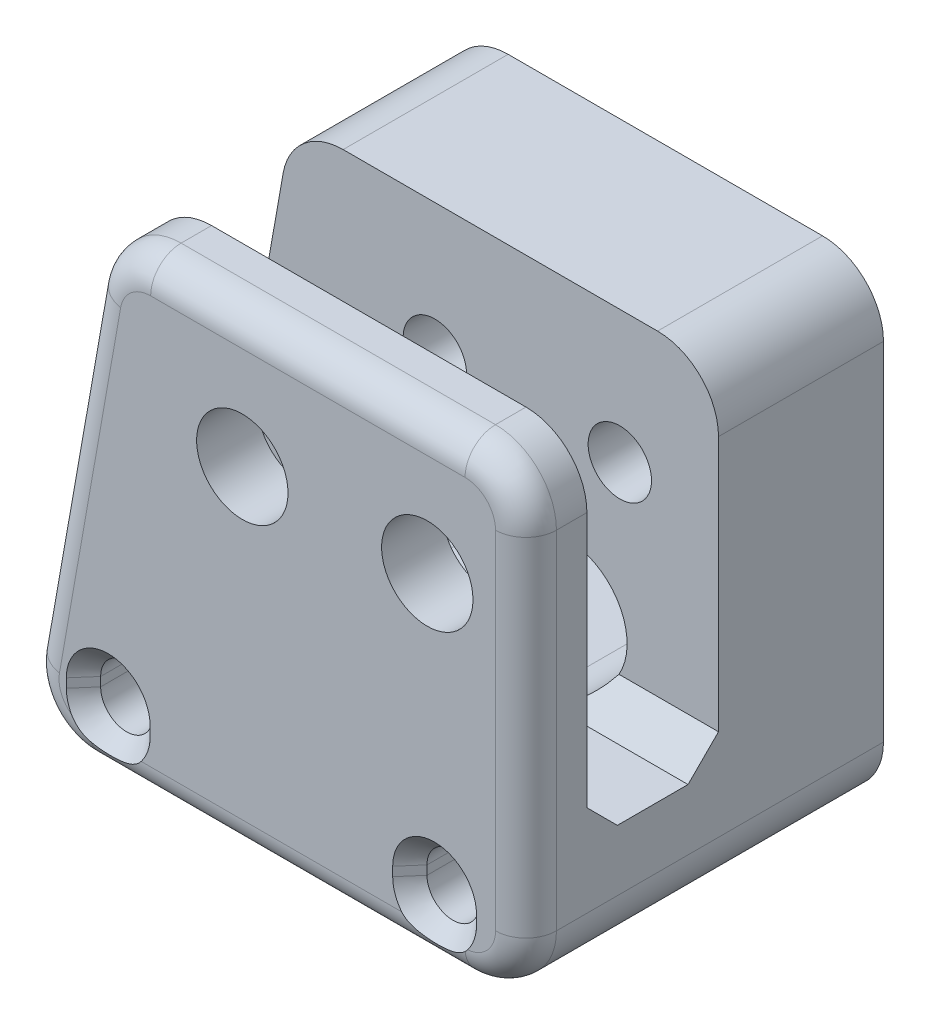
SolidWorks part; units mm, degrees
material "PET"
ref_plane "Front Plane" through (0, 0, 0) normal (0, 0, 1) x (1, 0, 0)
ref_plane "Top Plane" through (0, 0, 0) normal (0, 1, 0) x (1, 0, 0)
ref_plane "Right Plane" through (0, 0, 0) normal (1, 0, 0) x (0, 0, -1)
sketch "Sketch1" plane through (0, 0, 0) normal (0, 0, 1) x (1, 0, 0)
  line L0 (9.9949, 9.271) -> (9.9949, -24.688) construction
  line L2 (9.9949, 9.271) -> (9.9949, -15.163)
  line L3 (9.9949, 9.271) -> (-12.2301, 9.271)
  line L4 (-12.2301, 9.271) -> (-16.5385, -15.163)
  line L5 (-16.5385, -15.163) -> (9.9949, -15.163)
  point P3 (0, 0)
  point P4 (0, 0)
  point P5 (0, 0)
  point P9 (0, 0)
  point P11 (0, 0)
  point P12 (0, 0)
  dimension "D1" = 9.525
  dimension "D2" = 80
  dimension "D3" = 22.225
extrude "Boss-Extrude1" add sketch "Sketch1" along normal blind 3.175
extrude "Boss-Extrude2" add sketch "Sketch1<2>" against normal up to surface (8.5979 mm away) from offset 6.858 separate body offset against normal yes
sketch "Sketch1<2>" plane through (0, 0, 0) normal (0, 0, 1) x (1, 0, 0) same geometry as "Sketch1"
sketch "Sketch3" plane through (0, 0, -6.858) normal (0, 0, 1) x (1, 0, 0)
  line L0 (9.9949, 9.271) -> (9.9949, -15.163) construction
  line L1 (-16.5385, -15.163) -> (-12.2301, 9.271) construction
  line L2 (9.9949, -15.163) -> (-16.5385, -15.163) construction
  line L3 (9.9949, -8.813) -> (9.9949, -15.163)
  line L4 (-16.5385, -15.163) -> (-15.4188, -8.813)
  line L5 (9.9949, -15.163) -> (-16.5385, -15.163)
  line L6 (9.9949, -8.813) -> (-15.4188, -8.813)
  dimension "D1" = 6.35
extrude "Boss-Extrude3" add sketch "Sketch3" along normal up to surface (6.858 mm away) up to face at (-2.1947, -2.946, 0)
hole_wizard "CSK SLOT for #2 Flat Head Machine Screw1" positions "Sketch4" profile "Sketch5" size "#2" standard "ANSI Inch" slot yes end condition through all
sketch "Sketch4" plane through (0, 0, 3.175) normal (0, 0, 1) x (1, 0, 0)
  line L0 (5.2324, -13.5755) -> (5.2324, -10.4005) construction
  line L1 (9.9949, -15.163) -> (9.9949, 9.271) construction
  line L2 (-16.5385, -15.163) -> (9.9949, -15.163) construction
  point P0 (5.2324, -11.988)
  point P2 (-11.776, -11.988)
  dimension "D1" = 3.175
  dimension "D2" = 3.175
  dimension "D3" = 4.7625
  dimension "D4" = 4.7625
sketch "Sketch5" plane through (5.2324, -11.988, 3.175) normal (1, 0, 0) x (0, -1, 0)
  line L0 (0, 0) -> (0, 18.6309)
  line L1 (0, 18.6309) -> (1.3525, 18.6309)
  line L2 (1.3525, 18.6309) -> (1.3525, 0.9569)
  line L3 (1.3525, 0.9569) -> (2.1844, 0)
  line L5 (2.1844, 0) -> (0, 0)
  line L6 (-1.3525, 0.9569) -> (-2.1844, 0) construction
  line L11 (0, -6.35) -> (0, 107.95) construction
  dimension "Thru Hole Dia." = 2.7051
  dimension "Thru Hole Depth" = 18.6309
  dimension "Near C'Sink Dia." = 4.3688
  dimension "Near C'Sink Angle" = 82
fillet "Fillet1" radius 3.175 6 edges at (-12.2301, 9.271, -11.157) (-12.2301, 9.271, 1.5875) (9.9949, 9.271, 1.5875) (9.9949, 9.271, -11.157) (9.9949, -15.163, -6.1405) (-16.5385, -15.163, -6.1405)
chamfer "Chamfer1" distance 1.5875 angle 45 2 edges at (-2.7119, -8.813, 0) (-2.7119, -8.813, -6.858)
hole_wizard "3/16 (0.1875) Diameter Hole1" positions "Sketch6" profile "Sketch7" hole size "3/16" standard "ANSI Inch" end condition up to next
sketch "Sketch6" plane through (0, 0, 3.175) normal (0, 0, 1) x (1, 0, 0)
  point P0 (4.8514, 2.3622)
  point P3 (-4.7879, 2.3622)
sketch "Sketch7" plane through (4.8514, 2.3622, 3.175) normal (1, 0, 0) x (0, -1, 0)
  line L0 (0, 0) -> (0, 3.175)
  line L1 (0, 3.175) -> (2.3812, 3.175)
  line L2 (2.3812, 3.175) -> (2.3812, 0)
  line L5 (2.3812, 0) -> (0, 0)
  line L11 (0, -6.35) -> (0, 107.95) construction
  dimension "Thru Hole Dia." = 4.7625
  dimension "Thru Hole Depth" = 3.175
hole_wizard "#0 Clearance Hole1" positions "Sketch8" profile "Sketch9" hole size "#0" standard "ANSI Inch" end condition up to next
sketch "Sketch8" plane through (0, 0, -15.4559) normal (0, 0, -1) x (-1, 0, 0)
  circle A0 centre (4.7879, 2.3622) radius 2.3812 construction
  circle A1 centre (-4.8514, 2.3622) radius 2.3812 construction
  point P0 (-4.8514, 2.3622)
  point P2 (4.7879, 2.3622)
sketch "Sketch9" plane through (4.8514, 2.3622, -15.4559) normal (1, 0, 0) x (0, 1, 0)
  line L0 (0, 0) -> (0, 8.5979)
  line L1 (0, 8.5979) -> (0.9271, 8.5979)
  line L2 (0.9271, 8.5979) -> (0.9271, 0)
  line L5 (0.9271, 0) -> (0, 0)
  line L11 (0, -6.35) -> (0, 107.95) construction
  dimension "Thru Hole Dia." = 1.8542
  dimension "Thru Hole Depth" = 8.5979
hole_wizard "Hole1" positions "Sketch10" profile "Sketch11" legacy
sketch "Sketch10" plane through (0, 0, -6.858) normal (0, 0, 1) x (1, 0, 0)
  point P0 (4.8514, 2.3622)
  point P3 (-4.7879, 2.3622)
sketch "Sketch11" plane through (4.8514, 2.3622, -6.858) normal (1, 0, 0) x (0, -1, 0)
  line L0 (0, 0) -> (0, 3.048)
  line L1 (0, 3.048) -> (1.524, 3.048)
  line L2 (1.524, 3.048) -> (1.651, 0)
  line L3 (1.651, 0) -> (0, 0)
  line L4 (0, 110) -> (0, -10) construction
  dimension "Minor Diameter" = 3.048
  dimension "Depth" = 3.048
  dimension "Major Diameter" = 3.302
sketch "Sketch13" plane through (0, 0, -15.4559) normal (0, 0, -1) x (-1, 0, 0)
  line L0 (-2.0574, -5.638) -> (6.848, -5.638) construction
  line L1 (-2.0574, -2.463) -> (6.848, -2.463)
  line L2 (-2.0574, -8.813) -> (6.848, -8.813)
  line L3 (15.8814, -11.4367) -> (12.6927, 6.6473) construction
  line L4 (-9.9949, 6.096) -> (-9.9949, -11.988) construction
  line L5 (15.4188, -8.813) -> (-9.9949, -8.813) construction
  arc A0 (-2.0574, -2.463) -> (-2.0574, -8.813) centre (-2.0574, -5.638) ccw
  arc A1 (6.848, -8.813) -> (6.848, -2.463) centre (6.848, -5.638) ccw
  point P2 (2.3953, -5.638)
  point P7 (-5.2324, -5.638)
  point P8 (10.023, -5.638)
  dimension "D1" = 4.7625
  dimension "D2" = 4.7625
  dimension "D3" = 6.35
extrude "Cut-Extrude2" cut sketch "Sketch13" against normal up to next
fillet "Fillet3" radius 1.5875 8 edges at (9.065, -14.2331, 3.175) (-2.9674, -15.163, 3.175) (-15.1868, -14.0288, 3.175) (-14.2871, -2.3947, 3.175) (-11.6068, 8.5282, 3.175) (-1.373, 9.271, 3.175) (9.065, 8.3411, 3.175) (9.9949, -2.946, 3.175)
